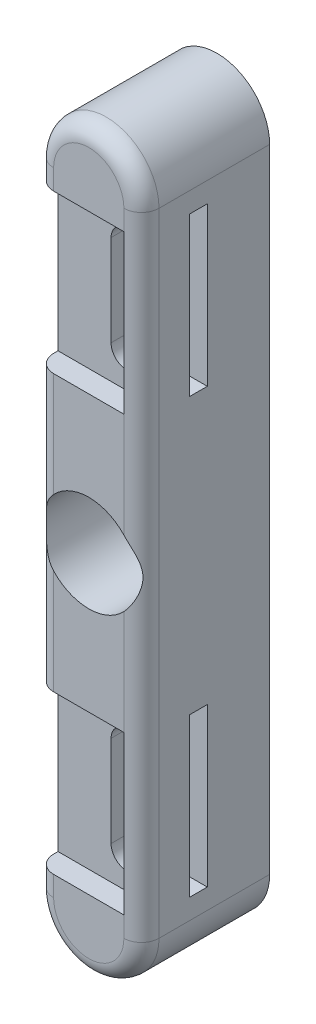
SolidWorks part; units mm, degrees
ref_plane "Alzado" through (0, 0, 0) normal (0, 0, 1) x (1, 0, 0)
ref_plane "Planta" through (0, 0, 0) normal (0, 1, 0) x (1, 0, 0)
ref_plane "Vista lateral" through (0, 0, 0) normal (1, 0, 0) x (0, 0, -1)
sketch "Croquis1" plane through (0, 0, 0) normal (0, 0, 1) x (1, 0, 0)
  line L0 (58.9, -7.25) -> (58.9, 64.75) construction
  line L1 (52.9, -7.25) -> (52.9, 64.75)
  line L2 (64.9, -7.25) -> (64.9, 64.75)
  line L3 (-29.1, 70.75) -> (64.9, 70.75) construction
  arc A0 (52.9, -7.25) -> (64.9, -7.25) centre (58.9, -7.25) ccw
  arc A1 (64.9, 64.75) -> (52.9, 64.75) centre (58.9, 64.75) ccw
  arc A3 (58.9, -13.25) -> (64.9, -7.25) centre (58.9, -7.25) ccw construction
  point P4 (58.9, 28.75)
  dimension "D1" = 6
extrude "Saliente-Extruir1" add sketch "Croquis1" along normal up to surface (14.6 mm away) contours A0 L2 A1 L1
fillet "Redondeo1" radius 2 4 edges at (58.9, 70.75, 14.6) (64.9, 28.75, 14.6) (58.9, -13.25, 14.6) (52.9, 28.75, 14.6)
sketch "Croquis2" plane through (0, 0, 14.6) normal (0, 0, 1) x (1, 0, 0)
  line L0 (46.8348, -4.9448) -> (62.9, -4.9448)
  line L1 (46.8348, -4.9448) -> (46.8348, 13.0552)
  line L2 (62.9, -4.9448) -> (62.9, 13.0552)
  line L3 (46.8348, 13.0552) -> (62.9, 13.0552)
  line L5 (62.9, -7.25) -> (62.9, 64.75) construction
  line L6 (62.9, 28.75) -> (50062.9, 28.75) construction
  line L7 (62.9, 62.4448) -> (62.9, 44.4448)
  line L8 (46.8348, 44.4448) -> (62.9, 44.4448)
  line L9 (46.8348, 62.4448) -> (46.8348, 44.4448)
  line L10 (46.8348, 62.4448) -> (62.9, 62.4448)
  point P8 (62.9, 28.75)
  dimension "D1" = 18
extrude "Cortar-Extruir1" cut sketch "Croquis2" against normal blind 2.5
sketch "Croquis3" plane through (0, 0, 14.6) normal (0, 0, 1) x (1, 0, 0)
  line L0 (58.9, 64.75) -> (58.9, -7.25) construction
  circle A0 centre (58.9, 28.75) radius 5.5
  dimension "D1" = 11
extrude "Cortar-Extruir2" cut sketch "Croquis3" against normal through all contours A0
sketch "Croquis4" plane through (64.9, 0, 0) normal (1, 0, 0) x (0, 0, -1)
  line L0 (-14.6, 62.4448) -> (0, 62.4448) construction
  line L1 (0, 70.75) -> (0, -13.25) construction
  line L2 (-14.6, 44.4448) -> (0, 44.4448) construction
  line L3 (-14.6, 13.0552) -> (0, 13.0552) construction
  line L4 (-14.6, -4.9448) -> (0, -4.9448) construction
  line L5 (-12.6, 28.75) -> (0, 28.75) construction
  line L6 (-12.6, 64.75) -> (-12.6, -7.25) construction
  line L7 (-12.1, -4.9448) -> (-12.1, 13.0552) construction
  line L8 (-9.1, 13.0552) -> (-7.1, 13.0552)
  line L9 (-9.1, 13.0552) -> (-9.1, -4.9448)
  line L10 (-9.1, -4.9448) -> (-7.1, -4.9448)
  line L11 (-7.1, 13.0552) -> (-7.1, -4.9448)
  line L12 (-9.1, 62.4448) -> (-7.1, 62.4448)
  line L13 (-9.1, 44.4448) -> (-7.1, 44.4448)
  line L14 (-7.1, 44.4448) -> (-7.1, 62.4448)
  line L15 (-9.1, 44.4448) -> (-9.1, 62.4448)
  dimension "D1" = 3
  dimension "D2" = 2
extrude "Cortar-Extruir3" cut sketch "Croquis4" against normal blind 6.5
sketch "Croquis5" plane through (0, 0, 12.1) normal (0, 0, 1) x (1, 0, 0)
  line L0 (60.741, 9.2452) -> (60.741, 50009.2452) construction
  line L1 (52.9, 28.75) -> (64.9, 28.75) construction
  line L2 (52.9, 13.0552) -> (52.9, 44.4448) construction
  line L3 (64.9, 64.75) -> (64.9, -7.25) construction
  line L4 (60.741, 9.2452) -> (60.741, -1.1348) construction
  line L5 (62.541, 9.2452) -> (62.541, -1.1348)
  line L6 (58.941, 9.2452) -> (58.941, -1.1348)
  line L7 (62.9, 13.0552) -> (54.9, 13.0552) construction
  line L8 (60.741, 48.2548) -> (60.741, 58.6348) construction
  line L9 (62.541, 48.2548) -> (62.541, 58.6348)
  line L10 (58.941, 48.2548) -> (58.941, 58.6348)
  arc A0 (62.541, 9.2452) -> (58.941, 9.2452) centre (60.741, 9.2452) ccw
  arc A1 (58.941, -1.1348) -> (62.541, -1.1348) centre (60.741, -1.1348) ccw
  arc A2 (62.541, 48.2548) -> (58.941, 48.2548) centre (60.741, 48.2548) cw
  arc A3 (58.941, 58.6348) -> (62.541, 58.6348) centre (60.741, 58.6348) cw
  point P11 (60.741, 4.0552)
  point P25 (60.741, 53.4448)
  dimension "D1" = 1.8
  dimension "D2" = 10.38
  dimension "D3" = 3.81
extrude "Cortar-Extruir4" cut sketch "Croquis5" against normal through all
